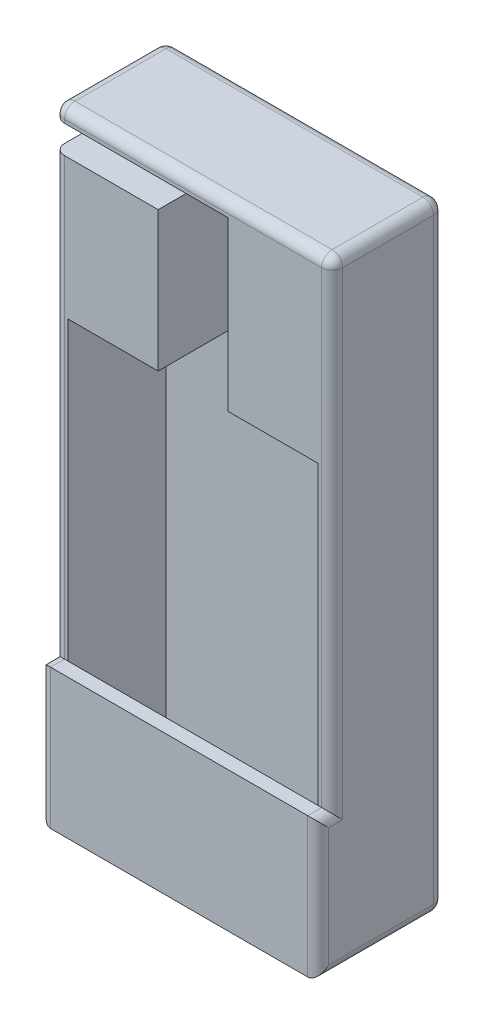
SolidWorks part; units mm, degrees
ref_plane "Front Plane" through (0, 0, 0) normal (0, 0, 1) x (1, 0, 0)
ref_plane "Top Plane" through (0, 0, 0) normal (0, 1, 0) x (1, 0, 0)
ref_plane "Right Plane" through (0, 0, 0) normal (1, 0, 0) x (0, 0, -1)
sketch "Sketch1" plane through (0, 0, 0) normal (0, 1, 0) x (1, 0, 0)
  line L0 (-22.733, -7.62) -> (-22.733, -10.16)
  line L1 (-25.273, -10.16) -> (25.273, -10.16)
  line L2 (-25.273, -10.16) -> (-25.273, 10.16)
  line L3 (-25.273, 10.16) -> (25.273, 10.16)
  line L4 (25.273, -10.16) -> (25.273, 10.16)
  line L5 (-25.273, -10.16) -> (25.273, 10.16) construction
  line L6 (-25.273, 10.16) -> (25.273, -10.16) construction
  line L7 (-22.733, -7.62) -> (22.733, -7.62)
  line L8 (-22.733, -7.62) -> (-22.733, 7.62)
  line L9 (-22.733, 7.62) -> (22.733, 7.62)
  line L10 (22.733, -7.62) -> (22.733, 7.62)
  line L11 (-22.733, -7.62) -> (22.733, 7.62) construction
  line L12 (-22.733, 7.62) -> (22.733, -7.62) construction
  line L13 (22.733, -7.62) -> (22.733, -10.16)
  line L14 (-22.733, -7.62) -> (-25.273, -7.62) construction
  line L15 (-20.193, -5.08) -> (-20.193, -10.16)
  line L17 (-20.193, -5.08) -> (-20.193, 5.08)
  line L18 (-20.193, 5.08) -> (20.193, 5.08)
  line L19 (20.193, -5.08) -> (20.193, 5.08)
  line L20 (-20.193, -5.08) -> (20.193, 5.08) construction
  line L21 (-20.193, 5.08) -> (20.193, -5.08) construction
  line L22 (20.193, -5.08) -> (20.193, -10.16)
  line L23 (-20.193, -5.08) -> (-22.733, -5.08) construction
  line L24 (-20.193, 5.08) -> (-20.193, 7.62) construction
  line L25 (0, -3.175) -> (0, 3.81) construction
  line L26 (-6.35, -3.175) -> (-6.35, 3.81)
  line L27 (6.35, -3.175) -> (6.35, 3.81)
  line L28 (-6.35, -3.175) -> (-6.35, -10.16)
  line L29 (6.35, -3.175) -> (6.35, -10.16)
  arc A1 (6.35, 3.81) -> (-6.35, 3.81) centre (0, 3.81) ccw
  point P0 (0, 0)
  point P6 (0, 0)
  point P11 (0, 0)
  dimension "D4" = 6.35
  dimension "D1" = 15.24
  dimension "D2" = 2.54
  dimension "D3" = 45.466
extrude "Boss-Extrude3" add sketch "Sketch1" along normal blind 5.588 contours A1 L3 L2 L1 L0 L8 L9 | A1 L9 L10 L13 L1 L4 L3 | L9 A1 | A1 L9 L8 L7 L15 L17 L18 | L15 L7 L0 L1 | L18 A1 L9 | A1 L18 L19 L22 L7 L10 L9 | L7 L22 L1 L13 region at (-21.463, 0, 8.89) region at (-22.4998, 0, 0) region at (-23.0573, 0, 8.89) region at (0, 0, -8.6557) region at (0, 0, -6.3086) region at (2.9848, 0, -9.7797) region at (13.9065, 0, -7.3868) region at (21.463, 0, 8.89)
extrude "Boss-Extrude4" add sketch "Sketch1<7>" along normal blind 73.66 from surface contours A1 L3 L2 L1 L0 L8 L9 | A1 L9 L10 L13 L1 L4 L3 | L9 A1 region at (-23.0573, 0, 8.89) region at (0, 0, -8.6557) region at (2.9848, 0, -9.7797) starting at face at (0, 5.588, 1.27)
sketch "Sketch1<7>" plane through (0, 0, 0) normal (0, 1, 0) x (1, 0, 0) same geometry as "Sketch1"
extrude "Boss-Extrude6" add sketch "Sketch1<8>" along normal blind 30.48 from surface contours A1 L3 L2 L1 L0 L8 L9 | A1 L9 L8 L7 L15 L17 L18 | A1 L18 L17 L15 L7 L28 L26 | L15 L7 L0 L1 | L28 L7 L15 L1 | A1 L9 L10 L13 L1 L4 L3 | A1 L18 L19 L22 L7 L10 L9 | A1 L27 L29 L7 L22 L19 L18 | L7 L29 L1 L22 | L7 L22 L1 L13 | L9 A1 region at (-21.463, 0, 8.89) region at (-22.4998, 0, 0) region at (-23.0573, 0, 8.89) region at (-13.2694, 0, 1.2681) region at (-13.2715, 0, 8.89) region at (0, 0, -8.6557) region at (13.2694, 0, 1.2681) region at (13.2715, 0, 8.89) region at (2.9848, 0, -9.7797) region at (13.9065, 0, -7.3868) region at (21.463, 0, 8.89) starting at face at (0, 79.248, 0.635)
sketch "Sketch1<8>" plane through (0, 0, 0) normal (0, 1, 0) x (1, 0, 0) same geometry as "Sketch1"
extrude "Boss-Extrude7" add sketch "Sketch1<9>" along normal blind 2.54 from surface contours L27 A1 L18 L26 L28 L7 L29 | L29 L7 L28 L1 | L18 A1 L9 | A1 L3 L2 L1 L0 L8 L9 | L15 L7 L0 L1 | A1 L9 L8 L7 L15 L17 L18 | L28 L7 L15 L1 | A1 L18 L17 L15 L7 L28 L26 | L9 A1 | A1 L18 L19 L22 L7 L10 L9 | A1 L9 L10 L13 L1 L4 L3 | A1 L27 L29 L7 L22 L19 L18 | L7 L29 L1 L22 | L7 L22 L1 L13 | L3 L4 L1 L2 region at (-21.463, 0, 8.89) region at (-22.4998, 0, 0) region at (-23.0573, 0, 8.89) region at (-13.2694, 0, 1.2681) region at (-13.2715, 0, 8.89) region at (0, 0, 1.274) region at (0, 0, 8.89) region at (0, 0, -8.6557) region at (0, 0, -6.3086) region at (13.2694, 0, 1.2681) region at (13.2715, 0, 8.89) region at (2.9848, 0, -9.7797) region at (13.9065, 0, -7.3868) region at (21.463, 0, 8.89) starting at face at (0, 109.728, -0.2746)
sketch "Sketch1<9>" plane through (0, 0, 0) normal (0, 1, 0) x (1, 0, 0) same geometry as "Sketch1"
sketch "Sketch4" plane through (0, 0, 10.16) normal (0, 0, 1) x (1, 0, 0)
  line L0 (-25.273, 112.268) -> (-25.273, 0) construction
  line L1 (-25.273, 0) -> (25.273, 0)
  line L2 (-25.273, 0) -> (-25.273, 25.4)
  line L3 (-25.273, 25.4) -> (25.273, 25.4)
  line L4 (25.273, 0) -> (25.273, 25.4)
  line L5 (25.273, 112.268) -> (25.273, 0) construction
  line L7 (-25.273, 0) -> (25.273, 0) construction
  point P8 (25.273, 34.202)
  point P9 (-25.273, 12.3673)
  dimension "D1" = 25.4
extrude "Boss-Extrude10" add sketch "Sketch4" along normal blind 2.54
fillet "Fillet1" radius 1.905 15 edges at (0, 0, -10.16) (-25.273, 56.134, -10.16) (-25.273, 68.834, 10.16) (-25.273, 0, 1.27) (25.273, 68.834, 10.16) (25.273, 56.134, -10.16) (25.273, 0, 1.27) (0, 112.268, -10.16) (25.273, 112.268, 0) (0, 112.268, 10.16) (-25.273, 112.268, 0) (-25.273, 25.4, 11.43) (-25.273, 12.7, 12.7) (25.273, 12.7, 12.7) (25.273, 25.4, 11.43)
sketch "Sketch3" plane through (0, 0, 10.16) normal (0, 0, 1) x (1, 0, 0)
  line L0 (-25.273, 112.268) -> (-25.273, 0) construction
  line L1 (-5.08, 109.728) -> (-25.273, 109.728)
  line L2 (-5.08, 109.728) -> (-5.08, 104.648)
  line L3 (-5.08, 104.648) -> (-25.273, 104.648)
  line L4 (-25.273, 109.728) -> (-25.273, 104.648)
  dimension "D1" = 5.08
extrude "Cut-Extrude3" cut sketch "Sketch3" against normal up to surface (17.78 mm away) up to face at (0, 68.453, -7.62)
